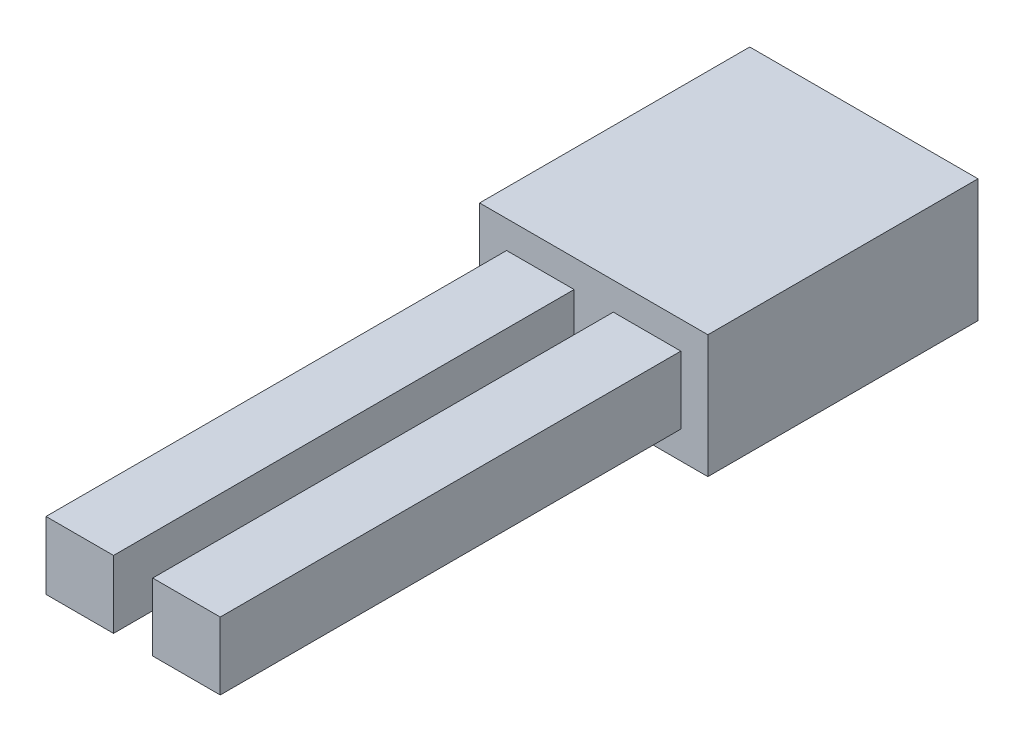
SolidWorks part; units mm, degrees
ref_plane "Front Plane" through (0, 0, 0) normal (0, 0, 1) x (1, 0, 0)
ref_plane "Top Plane" through (0, 0, 0) normal (0, 1, 0) x (1, 0, 0)
ref_plane "Right Plane" through (0, 0, 0) normal (1, 0, 0) x (0, 0, -1)
sketch "Sketch1" plane through (0, 0, 0) normal (0, 1, 0) x (1, 0, 0)
  line L1 (0, 0) -> (3.38, 0)
  line L2 (0, 0) -> (0, 4)
  line L3 (0, 4) -> (3.38, 4)
  line L4 (3.38, 0) -> (3.38, 4)
  dimension "D1" = 3.38
  dimension "D2" = 4
extrude "Boss-Extrude1" add sketch "Sketch1" along normal blind 1.82
sketch "Sketch2" plane through (0, 0, 0) normal (0, 0, 1) x (1, 0, 0)
  line L0 (0, 1.82) -> (0, 0) construction
  line L1 (0.4, 1.41) -> (1.4, 1.41)
  line L2 (0.4, 1.41) -> (0.4, 0.41)
  line L3 (0.4, 0.41) -> (1.4, 0.41)
  line L4 (1.4, 1.41) -> (1.4, 0.41)
  line L5 (1.98, 1.41) -> (2.98, 1.41)
  line L6 (1.98, 1.41) -> (1.98, 0.41)
  line L7 (1.98, 0.41) -> (2.98, 0.41)
  line L8 (2.98, 1.41) -> (2.98, 0.41)
  line L9 (0, 1.82) -> (3.38, 1.82) construction
  line L10 (0, 0) -> (3.38, 0) construction
  line L11 (3.38, 1.82) -> (3.38, 0) construction
  dimension "D1" = 1
  dimension "D2" = 1
  dimension "D3" = 0.4
  dimension "D4" = 0.41
  dimension "D5" = 0.41
  dimension "D6" = 1
  dimension "D7" = 1
  dimension "D8" = 0.41
  dimension "D9" = 0.41
  dimension "D10" = 0.4
extrude "Boss-Extrude2" add sketch "Sketch2" along normal blind 6.82
